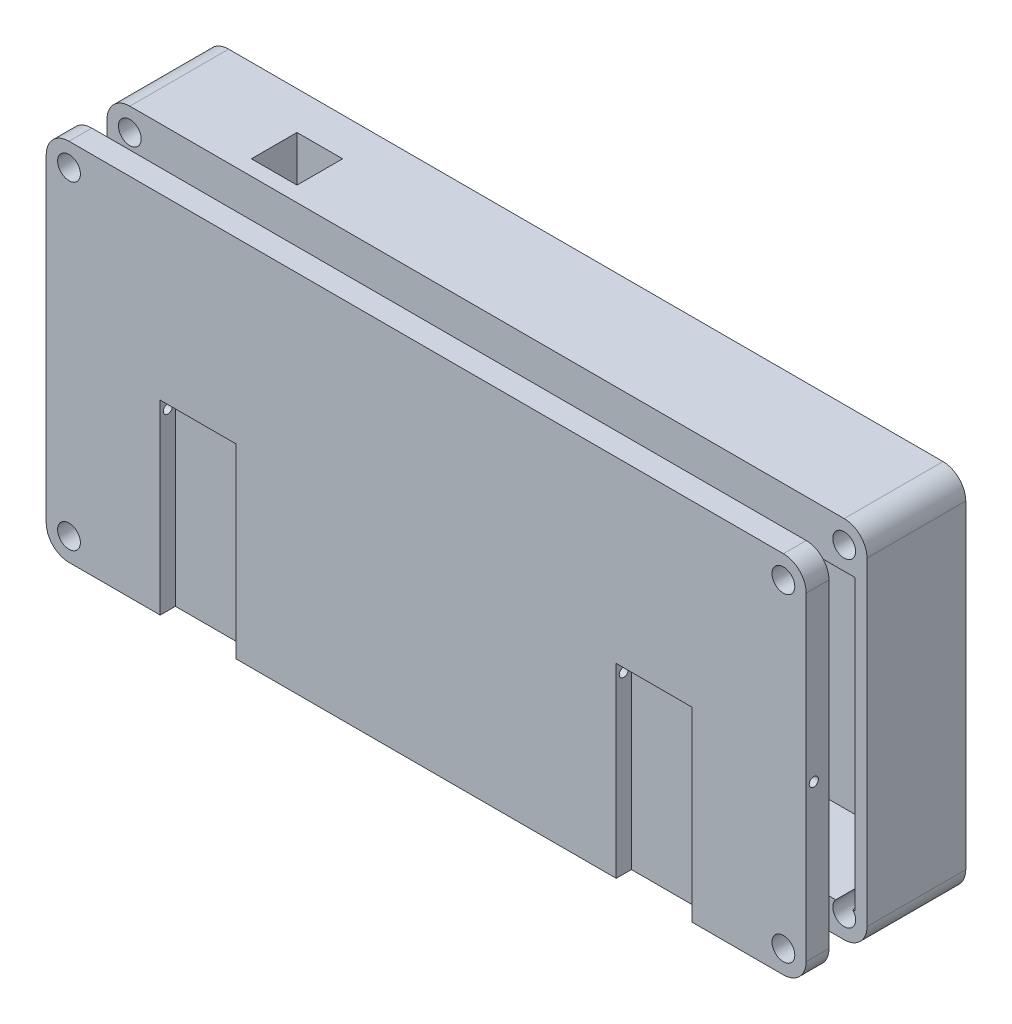
SolidWorks part; units mm, degrees
ref_plane "前视" through (0, 0, 0) normal (0, 0, 1) x (1, 0, 0)
ref_plane "上视" through (0, 0, 0) normal (0, 1, 0) x (1, 0, 0)
ref_plane "右视" through (0, 0, 0) normal (1, 0, 0) x (0, 0, -1)
sketch "草图1" plane through (0, 0, 0) normal (1, 0, 0) x (0, 0, -1)
  line L0 (0, 0) -> (13, 0)
  line L1 (0, 48) -> (0, 0)
  line L2 (13, 0) -> (13, 48)
  line L3 (13, 48) -> (0, 48)
  dimension "D1" = 13
  dimension "D2" = 48
extrude "凸台-拉伸2" add sketch "草图1" along normal blind 100 contours L1 L0 L2 L3
sketch "草图4" plane through (0, 0, 0) normal (0, 0, 1) x (1, 0, 0)
  line L0 (50, 0) -> (50, 46) construction
  line L1 (100, 0) -> (0, 0) construction
  line L2 (100, 48) -> (0, 48) construction
  line L3 (100, 48) -> (100, 0) construction
  line L4 (1.55, 42) -> (98.45, 42)
  line L5 (1.55, 42) -> (1.55, 4)
  line L6 (1.55, 4) -> (98.45, 4)
  line L7 (98.45, 42) -> (98.45, 4)
  line L8 (1.55, 42) -> (98.45, 4) construction
  line L9 (1.55, 4) -> (98.45, 42) construction
  line L10 (81.945, 37.525) -> (82.945, 36.525)
  line L11 (18.055, 37.525) -> (81.945, 37.525)
  line L12 (17.055, 36.525) -> (17.055, 10.475)
  line L13 (18.055, 9.475) -> (81.945, 9.475)
  line L14 (82.945, 36.525) -> (82.945, 10.475)
  line L15 (17.055, 37.525) -> (82.945, 9.475) construction
  line L16 (17.055, 9.475) -> (82.945, 37.525) construction
  line L17 (17.055, 36.525) -> (18.055, 37.525)
  line L18 (17.055, 10.475) -> (18.055, 9.475)
  line L19 (81.945, 9.475) -> (82.945, 10.475)
  point P6 (50, 23)
  point P13 (50, 23.5)
  dimension "D2" = 38
  dimension "D3" = 96.9
  dimension "D4" = 1.55
  dimension "D6" = 65.89
  dimension "D7" = 28.05
  dimension "D8" = 2
extrude "切除-拉伸3" cut sketch "草图4" against normal through all contours L14 L11 L12 L13 region at (50, 23.5, 0)
extrude "切除-拉伸4" cut sketch "草图4<3>" against normal offset from surface (11 mm away) 2 contours L7 L4 L5 L6 L11 L14 L13 L12 region at (50, 40.9592, 0) up to face at (50, 23.5, -13)
sketch "草图4<3>" plane through (0, 0, 0) normal (0, 0, 1) x (1, 0, 0) same geometry as "草图4"
chamfer "倒角4" distance 2 angle 60 8 edges at (17.055, 23.5, -13) (17.555, 37.025, -13) (50, 37.525, -13) (82.445, 37.025, -13) (82.945, 23.5, -13) (82.445, 9.975, -13) (50, 9.475, -13) (17.555, 9.975, -13) first distance on face at (17.055, 23.5, -12) first distance on face at (17.555, 37.025, -12) first distance on face at (50, 37.525, -12) first distance on face at (82.445, 37.025, -12) first distance on face at (82.945, 23.5, -12) first distance on face at (82.445, 9.975, -12) first distance on face at (50, 9.475, -12) first distance on face at (17.555, 9.975, -12)
fillet "圆角1" radius 3 4 edges at (0, 0, -6.5) (100, 0, -6.5) (0, 48, -6.5) (100, 48, -6.5)
sketch "草图12" plane through (0, 48, 0) normal (0, 1, 0) x (1, 0, 0)
  line L0 (0, 0) -> (0, 13) construction
  line L1 (97, 13) -> (3, 13) construction
  line L3 (23, 2) -> (17, 2)
  line L4 (23, 2) -> (23, 8)
  line L5 (23, 8) -> (17, 8)
  line L6 (17, 2) -> (17, 8)
  line L7 (23, 2) -> (17, 8) construction
  line L8 (23, 8) -> (17, 2) construction
  circle A0 centre (20, 5) radius 3
  dimension "D1" = 20
  dimension "D2" = 6
  dimension "D3" = 8
extrude "切除-拉伸18" cut sketch "草图12" against normal up to next contours A0 | A0 L6 L3 | A0 L5 L6 | A0 L4 L5 | A0 L3 L4 region at (22.3299, 48, -2.6701) region at (17.6701, 48, -2.6701) region at (20, 48, -5) region at (22.3299, 48, -7.3299) region at (17.6701, 48, -7.3299)
sketch "草图7" plane through (0, 0, 0) normal (0, 0, 1) x (1, 0, 0)
  line L4 (0, 45) -> (0, 3)
  line L5 (3, 0) -> (97, 0)
  line L6 (100, 3) -> (100, 45)
  line L7 (97, 48) -> (3, 48)
  line L8 (0, 45) -> (0, 3)
  line L9 (3, 0) -> (97, 0)
  line L10 (100, 3) -> (100, 45)
  line L11 (97, 48) -> (3, 48)
  arc A4 (0, 3) -> (3, 0) centre (3, 3) ccw
  arc A5 (97, 0) -> (100, 3) centre (97, 3) ccw
  arc A6 (100, 45) -> (97, 48) centre (97, 45) ccw
  arc A7 (3, 48) -> (0, 45) centre (3, 45) ccw
  arc A8 (0, 3) -> (3, 0) centre (3, 3) ccw
  arc A9 (97, 0) -> (100, 3) centre (97, 3) ccw
  arc A10 (100, 45) -> (97, 48) centre (97, 45) ccw
  arc A11 (3, 48) -> (0, 45) centre (3, 45) ccw
  dimension "D1" = 0
extrude "凸台-拉伸3" add sketch "草图7" along normal blind 3 from offset 5 separate body
sketch "草图8" plane through (0, 0, 8) normal (0, 0, 1) x (1, 0, 0)
  line L0 (50, 48) -> (50, 0) construction
  line L1 (3, 0) -> (97, 0)
  line L2 (15, 0) -> (15, 24)
  line L3 (75, 0) -> (85, 0)
  line L4 (0, 45) -> (0, 3)
  line L5 (3, 0) -> (97, 0)
  line L6 (100, 3) -> (100, 45)
  line L7 (97, 48) -> (3, 48)
  line L8 (0, 45) -> (0, 3)
  line L9 (75, 0) -> (75, 24)
  line L10 (100, 3) -> (100, 45)
  line L11 (97, 48) -> (3, 48)
  line L12 (75, 24) -> (85, 24)
  line L13 (85, 0) -> (85, 24)
  line L14 (25, 0) -> (25, 24)
  line L15 (25, 24) -> (15, 24)
  line L17 (15, 24) -> (25, 24)
  line L18 (15, 24) -> (15, 24.5)
  line L19 (15, 24.5) -> (25, 24.5)
  line L20 (25, 24) -> (25, 24.5)
  line L21 (75, 24) -> (85, 24)
  line L22 (75, 24) -> (75, 24.5)
  line L23 (75, 24.5) -> (85, 24.5)
  line L24 (85, 24) -> (85, 24.5)
  arc A4 (3, 48) -> (0, 45) centre (3, 45) ccw
  arc A5 (0, 3) -> (3, 0) centre (3, 3) ccw
  arc A6 (97, 0) -> (100, 3) centre (97, 3) ccw
  arc A7 (100, 45) -> (97, 48) centre (97, 45) ccw
  arc A8 (3, 48) -> (0, 45) centre (3, 45) ccw
  arc A9 (0, 3) -> (3, 0) centre (3, 3) ccw
  arc A10 (97, 0) -> (100, 3) centre (97, 3) ccw
  arc A11 (100, 45) -> (97, 48) centre (97, 45) ccw
  line M13 (3, 0) -> (97, 0)
  dimension "D2" = 10
  dimension "D3" = 24
  dimension "D4" = 50
  dimension "D5" = 0.5
  dimension "D6" = 0.5
  dimension "D1" = 0
extrude "切除-拉伸9" cut sketch "草图8" against normal blind 2 contours L14 L15 L2 L1 | L13 L12 L9 M13 region at (20, 12, 8) region at (80, 12, 8)
sketch "草图9" plane through (75, 0, 0) normal (1, 0, 0) x (0, 0, -1)
  line L0 (-6, 24) -> (-8, 24) construction
  line L1 (-7, 24) -> (-7, 22.9259) construction
  circle A0 centre (-7, 23) radius 0.6
  dimension "D1" = 1
extrude "切除-拉伸10" cut sketch "草图9" against normal through all both and the other way through all
sketch "草图10" plane through (0, 0, 8) normal (0, 0, 1) x (1, 0, 0)
  line L0 (0, 24) -> (78.5549, 24) construction
  line L1 (0, 45) -> (0, 3) construction
  line L2 (50, 48) -> (50, 3.3947) construction
  line L3 (97, 48) -> (3, 48) construction
  circle A0 centre (3, 45) radius 1.5
  arc A1 (3, 48) -> (0, 45) centre (3, 45) ccw construction
  circle A3 centre (97, 45) radius 1.5
  circle A4 centre (97, 3) radius 1.5
  circle A5 centre (3, 3) radius 1.5
  dimension "D1" = 3
extrude "切除-拉伸12" cut sketch "草图10" against normal through all
extrude "切除-拉伸16" cut sketch "草图8<4>" against normal blind 1 contours L15 L20 L19 L18 | L12 L24 L23 L22 region at (20, 24.25, 8) region at (80, 24.25, 8)
sketch "草图8<4>" plane through (0, 0, 8) normal (0, 0, 1) x (1, 0, 0) same geometry as "草图8"
